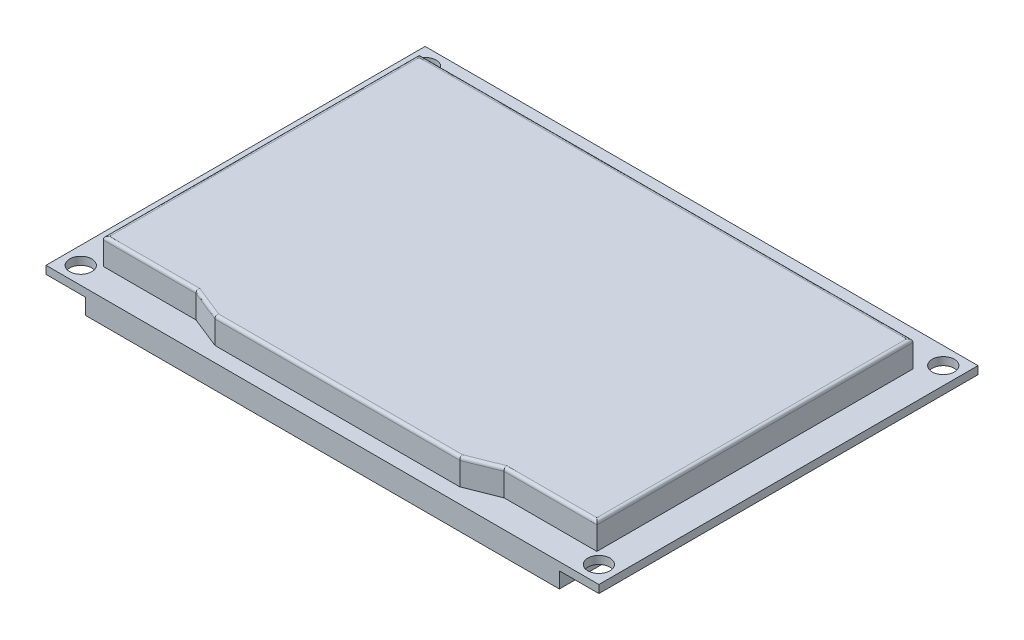
SolidWorks part; units mm, degrees
ref_plane "Front Plane" through (0, 0, 0) normal (0, 0, 1) x (1, 0, 0)
ref_plane "Top Plane" through (0, 0, 0) normal (0, 1, 0) x (1, 0, 0)
ref_plane "Right Plane" through (0, 0, 0) normal (1, 0, 0) x (0, 0, -1)
sketch "Sketch1" plane through (0, 0, 0) normal (0, 1, 0) x (1, 0, 0)
  line L0 (-2.2, 45.8) -> (-2.2, 48) construction
  line L1 (0, 0) -> (-70, 0)
  line L2 (0, 0) -> (0, 48)
  line L3 (0, 48) -> (-70, 48)
  line L4 (-70, 0) -> (-70, 48)
  line L5 (-66.25, 43.5) -> (-3.75, 43.5) construction
  line L6 (-66.25, 43.5) -> (-66.25, 3.5) construction
  line L7 (-66.25, 3.5) -> (-3.75, 3.5) construction
  line L8 (-3.75, 43.5) -> (-3.75, 3.5) construction
  line L9 (-67.8, 2.2) -> (-67.8, 0) construction
  line L10 (0, 45.8) -> (-2.2, 45.8) construction
  line L11 (-38.6, 45.2) -> (-36.2, 45.2) construction
  line L12 (-70, 2.2) -> (-67.8, 2.2) construction
  line L13 (-36.2, 45.2) -> (-33.8, 45.2) construction
  line L14 (-33.8, 45.2) -> (-31.4, 45.2) construction
  line L15 (-68.2, 27.6) -> (-68.2, 25.2) construction
  line L16 (-68.2, 25.2) -> (-68.2, 22.8) construction
  line L17 (-68.2, 22.8) -> (-68.2, 20.4) construction
  line L19 (-65, 43) -> (-5, 43) construction
  line L20 (-65, 43) -> (-65, 0) construction
  line L21 (-65, 0) -> (-5, 0)
  line L22 (-5, 43) -> (-5, 0) construction
  circle A0 centre (-2.2, 45.8) radius 1.4
  circle A1 centre (-2.2, 2.2) radius 1.4
  circle A2 centre (-67.8, 2.2) radius 1.4
  circle A3 centre (-67.8, 45.8) radius 1.4
  circle A4 centre (-38.6, 45.2) radius 0.5
  circle A5 centre (-36.2, 45.2) radius 0.5
  circle A6 centre (-33.8, 45.2) radius 0.5
  circle A7 centre (-31.4, 45.2) radius 0.5
  circle A8 centre (-68.2, 27.6) radius 0.5
  circle A9 centre (-68.2, 25.2) radius 0.5
  circle A10 centre (-68.2, 22.8) radius 0.5
  circle A11 centre (-68.2, 20.4) radius 0.5
  point P9 (-35, 43.5)
  point P10 (-35, 48)
  point P31 (-35, 45.2)
  point P40 (-68.2, 24)
  point P41 (-70, 24)
  dimension "D6" = 2.8
  dimension "D8" = 1
  dimension "D1" = 48
  dimension "D2" = 70
  dimension "D3" = 40
  dimension "D4" = 62.5
  dimension "D5" = 4.5
  dimension "D7" = 2.2
  dimension "D9" = 2.8
  dimension "D10" = 7.2
  dimension "D11" = 7.2
  dimension "D12" = 1.8
  dimension "D13" = 5
  dimension "D14" = 5
  dimension "D15" = 5
extrude "Boss-Extrude1" add sketch "Sketch1" along normal blind 1 contours L4 L1 L2 L3 A11 A10 A9 A8 A7 A6 A5 A4 A3 A2 A1 A0 region at (-34.9687, 0, -23.98)
sketch "Sketch2" plane through (0, 1, 0) normal (0, 1, 0) x (1, 0, 0)
  line L0 (-54.5, 3.5) -> (-50.5, 1.9)
  line L1 (-66.25, 43.5) -> (-3.75, 43.5)
  line L2 (-66.25, 43.5) -> (-66.25, 3.5)
  line L3 (-66.25, 3.5) -> (-54.5, 3.5)
  line L4 (-3.75, 43.5) -> (-3.75, 3.5)
  line L5 (-50.5, 1.9) -> (-19.5, 1.9)
  line L6 (-19.5, 1.9) -> (-15.5, 3.5)
  line L7 (-35, 43.5) -> (-35, 1.9) construction
  line L8 (-15.5, 3.5) -> (-3.75, 3.5)
  point P12 (0, 0)
  point P13 (-35, 43.5)
  dimension "D1" = 1.6
  dimension "D2" = 39
  dimension "D3" = 4
extrude "Boss-Extrude2" add sketch "Sketch2" along normal blind 3.3
sketch "Sketch3" plane through (0, 0, 0) normal (0, -1, 0) x (1, 0, 0)
  line L1 (-65, -43) -> (-5, -43)
  line L2 (-65, -43) -> (-65, 0)
  line L3 (-65, 0) -> (-5, 0)
  line L4 (-5, -43) -> (-5, 0)
extrude "Boss-Extrude3" add sketch "Sketch3" along normal blind 2
fillet "Fillet1" radius 0.4 8 edges at (-35, 4.3, -43.5) (-3.75, 4.3, -23.5) (-9.625, 4.3, -3.5) (-17.5, 4.3, -2.7) (-35, 4.3, -1.9) (-52.5, 4.3, -2.7) (-60.375, 4.3, -3.5) (-66.25, 4.3, -23.5) curvature continuous yes
